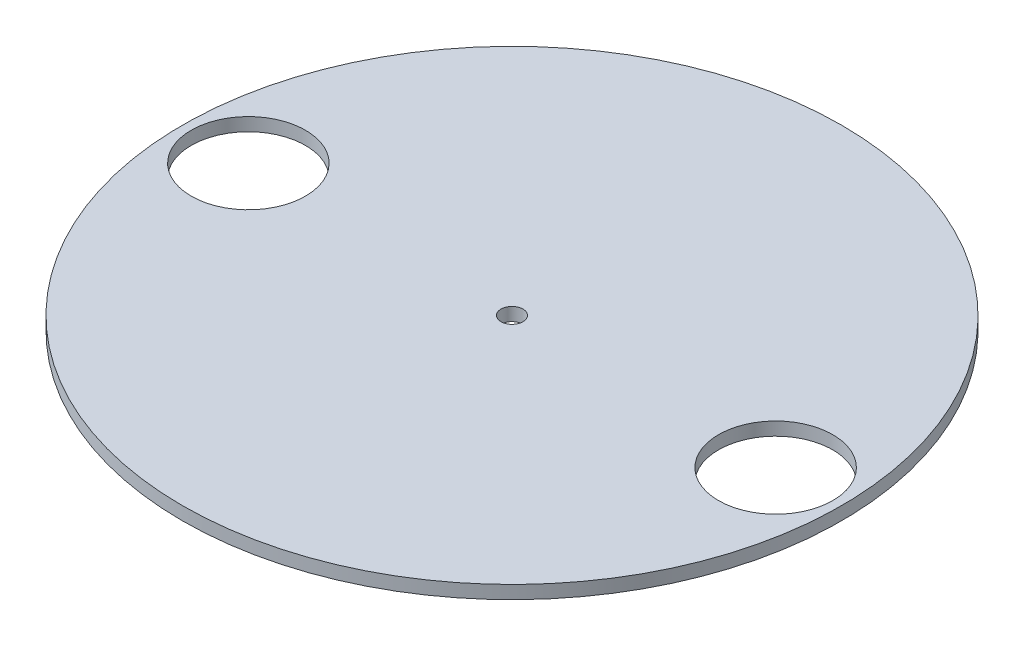
SolidWorks part; units mm, degrees
ref_plane "Front Plane" through (0, 0, 0) normal (0, 0, 1) x (1, 0, 0)
ref_plane "Top Plane" through (0, 0, 0) normal (0, 1, 0) x (1, 0, 0)
ref_plane "Right Plane" through (0, 0, 0) normal (1, 0, 0) x (0, 0, -1)
sketch "Sketch1" plane through (0, 0, 0) normal (0, 1, 0) x (1, 0, 0)
  line L0 (60, 0) -> (-60, 0)
  circle A3 centre (0, 0) radius 75
  circle A5 centre (-60, 0) radius 13
  circle A7 centre (60, 0) radius 13
  circle A9 centre (0, 0) radius 2.5
  point P15 (-60, 0)
  dimension "D1" = 75
  dimension "D2" = 120
  dimension "D3" = 13
  dimension "D4" = 13
  dimension "D5" = 2.5
extrude "Boss-Extrude1" add sketch "Sketch1" along normal blind 3 contours A7 A5 | A7 A5 region at (-74.7879, 0, 0)
extrude "Boss-Extrude2" add sketch "Sketch1<4>" along normal blind 3 contours A3 | A3 region at (-74.7879, 0, 0)
sketch "Sketch1<4>" plane through (0, 0, 0) normal (0, 1, 0) x (1, 0, 0) same geometry as "Sketch1"
